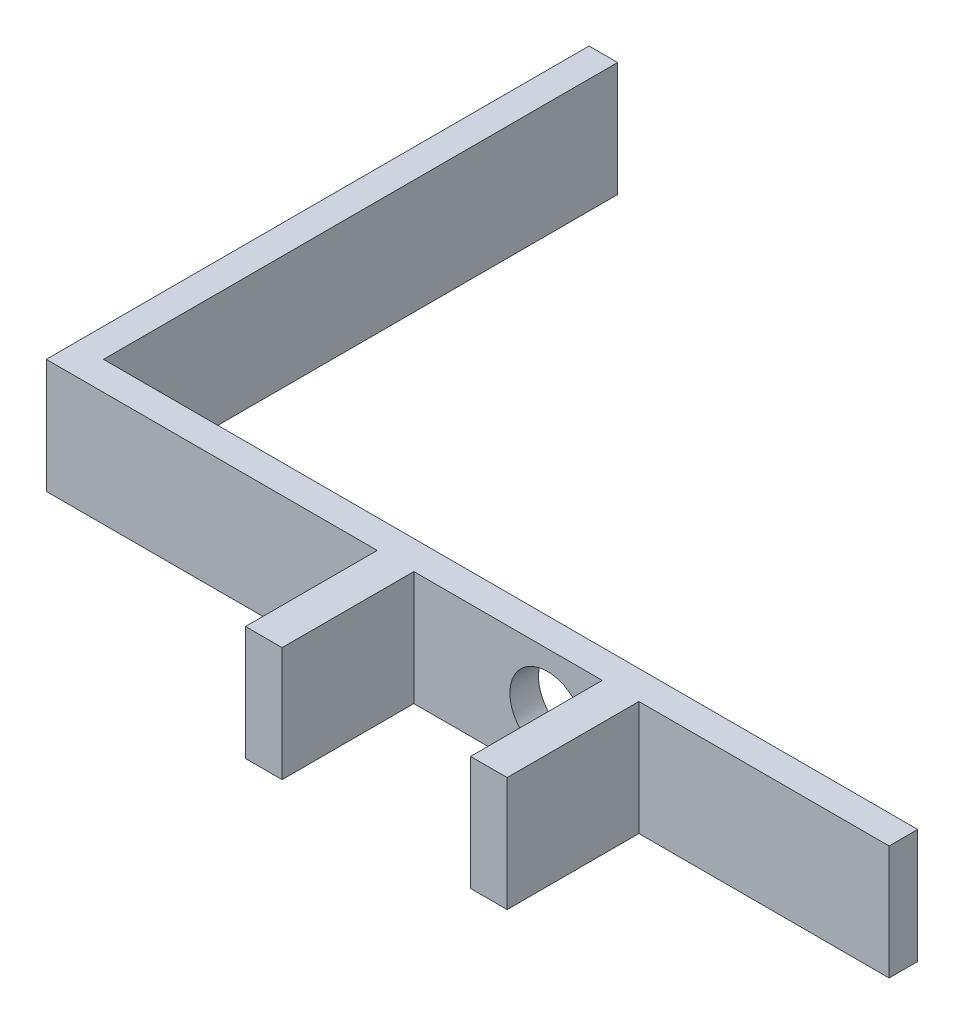
SolidWorks part; units mm, degrees
ref_plane "Front Plane" through (0, 0, 0) normal (0, 0, 1) x (1, 0, 0)
ref_plane "Top Plane" through (0, 0, 0) normal (0, 1, 0) x (1, 0, 0)
ref_plane "Right Plane" through (0, 0, 0) normal (1, 0, 0) x (0, 0, -1)
sketch "Sketch1" plane through (0, 0, 0) normal (0, 1, 0) x (1, 0, 0)
  line L1 (0, 0) -> (3.9688, 0)
  line L2 (0, 0) -> (0, 75.3427)
  line L3 (0, 75.3427) -> (3.9688, 75.3427)
  line L4 (3.9688, 3.9688) -> (3.9688, 75.3427)
  line L5 (3.9688, 0) -> (116.9988, 0)
  line L7 (3.9688, 3.9688) -> (116.9988, 3.9688)
  line L8 (116.9988, 0) -> (116.9988, 3.9688)
  dimension "D1" = 3.9688
  dimension "D2" = 3.9688
  dimension "D3" = 71.374
  dimension "D4" = 113.03
extrude "Boss-Extrude1" add sketch "Sketch1" along normal mid plane 15.875
sketch "Sketch2" plane through (0, 0, 0) normal (0, 0, 1) x (1, 0, 0)
  line L0 (116.9988, 7.9375) -> (116.9988, -7.9375) construction
  circle A0 centre (69.5643, 0) radius 5.207
  dimension "D1" = 47.4345
  dimension "D2" = 10.414
extrude "Cut-Extrude1" cut sketch "Sketch2" against normal up to surface (3.9688 mm away) up to face at (60.4838, 0, -3.9688)
sketch "Sketch4" plane through (0, 0, 0) normal (0, 0, 1) x (1, 0, 0)
  line L0 (0, -7.9375) -> (116.9988, -7.9375) construction
  line L1 (0, 7.9375) -> (116.9988, 7.9375) construction
  line L2 (45.9423, 7.9375) -> (51.0223, 7.9375)
  line L3 (45.9423, 7.9375) -> (45.9423, -7.9375)
  line L4 (45.9423, -7.9375) -> (51.0223, -7.9375)
  line L5 (51.0223, 7.9375) -> (51.0223, -7.9375)
  line L7 (77.1843, 7.9375) -> (82.2643, 7.9375)
  line L8 (77.1843, 7.9375) -> (77.1843, -7.9375)
  line L9 (77.1843, -7.9375) -> (82.2643, -7.9375)
  line L10 (82.2643, 7.9375) -> (82.2643, -7.9375)
  circle A0 centre (69.5643, 0) radius 5.207 construction
  dimension "D4" = 7.62
  dimension "D1" = 5.08
  dimension "D2" = 5.08
  dimension "D3" = 18.542
extrude "Boss-Extrude2" add sketch "Sketch4" along normal blind 18.288
